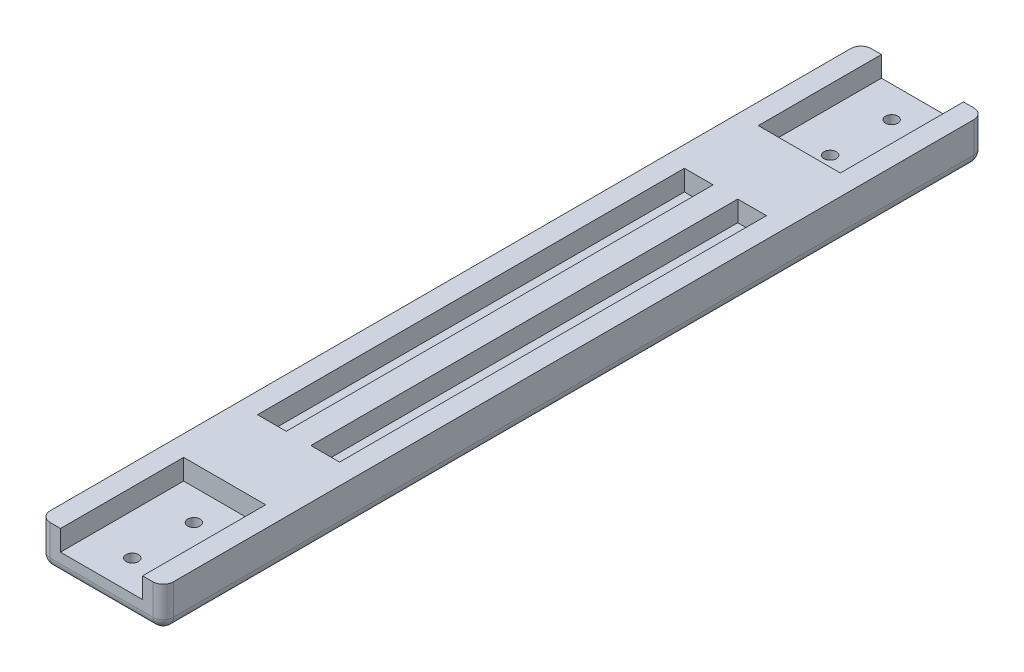
SolidWorks part; units mm, degrees
ref_plane "Front Plane" through (0, 0, 0) normal (0, 0, 1) x (1, 0, 0)
ref_plane "Top Plane" through (0, 0, 0) normal (0, 1, 0) x (1, 0, 0)
ref_plane "Right Plane" through (0, 0, 0) normal (1, 0, 0) x (0, 0, -1)
sketch "Sketch2" plane through (0, 0, 0) normal (0, 1, 0) x (1, 0, 0)
  line L1 (-15, 100) -> (15, 100)
  line L2 (-15, 100) -> (-15, -100)
  line L3 (-15, -100) -> (15, -100)
  line L4 (15, 100) -> (15, -100)
  line L5 (-15, 100) -> (15, -100) construction
  line L6 (-15, -100) -> (15, 100) construction
  point P0 (0, 0)
  dimension "D1" = 30
  dimension "D2" = 200
extrude "Boss-Extrude1" add sketch "Sketch2" along normal blind 10
sketch "Sketch3" plane through (0, 10, 0) normal (0, 1, 0) x (1, 0, 0)
  line L0 (15, 100) -> (-15, 100) construction
  line L1 (-10, 100) -> (10, 100)
  line L2 (-10, 100) -> (-10, 70)
  line L3 (-10, 70) -> (10, 70)
  line L4 (10, 100) -> (10, 70)
  line L5 (-15, 100) -> (-15, -100) construction
  line L6 (-15, -100) -> (15, -100) construction
  line L7 (-10, -100) -> (10, -100)
  line L8 (-10, -100) -> (-10, -70)
  line L9 (-10, -70) -> (10, -70)
  line L10 (10, -100) -> (10, -70)
  line L11 (15, -100) -> (15, 100) construction
  line L12 (3, 52) -> (10, 52)
  line L13 (3, 52) -> (3, -52)
  line L14 (3, -52) -> (10, -52)
  line L15 (10, 52) -> (10, -52)
  line L17 (-10, 52) -> (-3, 52)
  line L18 (-10, 52) -> (-10, -52)
  line L19 (-10, -52) -> (-3, -52)
  line L20 (-3, 52) -> (-3, -52)
  dimension "D1" = 20
  dimension "D2" = 30
  dimension "D3" = 5
  dimension "D4" = 5
  dimension "D5" = 20
  dimension "D6" = 30
  dimension "D7" = 18
  dimension "D8" = 18
  dimension "D9" = 5
  dimension "D10" = 7
  dimension "D11" = 7
  dimension "D12" = 5
  dimension "D13" = 18
  dimension "D14" = 18
extrude "Cut-Extrude1" cut sketch "Sketch3" against normal blind 5
fillet "Fillet1" radius 2.5 4 edges at (-15, 5, 100) (15, 5, 100) (-15, 5, -100) (15, 5, -100)
fillet "Fillet2" radius 2.5 8 edges at (-14.2678, 0, 99.2678) (-15, 0, 0) (-14.2678, 0, -99.2678) (0, 0, -100) (14.2678, 0, -99.2678) (15, 0, 0) (14.2678, 0, 99.2678) (0, 0, 100)
sketch "Sketch4" plane through (0, 10, 0) normal (0, 1, 0) x (1, 0, 0)
  line L0 (-10, 70) -> (10, 70) construction
  line L1 (5, 50) -> (8, 50)
  line L2 (5, 50) -> (5, -50)
  line L3 (5, -50) -> (8, -50)
  line L4 (8, 50) -> (8, -50)
  line L6 (15, -97.5) -> (15, 97.5) construction
  line L8 (-5, -50) -> (-8, -50)
  line L9 (-5, -50) -> (-5, 50)
  line L10 (-5, 50) -> (-8, 50)
  line L11 (-8, -50) -> (-8, 50)
  line L13 (10, 52) -> (3, 52) construction
  line L14 (3, -52) -> (10, -52) construction
  point P16 (-6.5, 50)
  dimension "D1" = 3
  dimension "D2" = 100
  dimension "D3" = 20
  dimension "D4" = 7
  dimension "D5" = 10
  dimension "D6" = 2
  dimension "D7" = 2
extrude "Cut-Extrude2" cut sketch "Sketch4" against normal blind 10
fillet "Fillet3" radius 1.5 8 edges at (5, 2.5, 50) (8, 2.5, 50) (5, 2.5, -50) (8, 2.5, -50) (-5, 2.5, 50) (-8, 2.5, 50) (-8, 2.5, -50) (-5, 2.5, -50)
hole_wizard "Ø3.0mm Dowel Hole1" positions "Sketch7" profile "Sketch6" hole size "Ø3.0" standard "ANSI Metric" end condition through all
sketch "Sketch7" plane through (0, 5, 0) normal (0, 1, 0) x (1, 0, 0)
  line L0 (10, 100) -> (-10, 100) construction
  line L1 (-10, 70) -> (10, 70) construction
  line L2 (10, 70) -> (10, 100) construction
  line L3 (10, 70) -> (10, 100) construction
  line L4 (10, -100) -> (10, -70) construction
  line L5 (10, -100) -> (10, -70) construction
  line L6 (10, -70) -> (-10, -70) construction
  line L7 (-10, -100) -> (10, -100) construction
  point P0 (0, 92.5)
  point P2 (0, 77.5)
  point P4 (0, -77.5)
  point P6 (0, -92.5)
  dimension "D1" = 7.5
  dimension "D2" = 7.5
  dimension "D3" = 10
  dimension "D4" = 10
  dimension "D5" = 10
  dimension "D6" = 10
  dimension "D7" = 7.5
  dimension "D8" = 7.5
sketch "Sketch6" plane through (0, 5, -92.5) normal (1, 0, 0) x (0, 0, 1)
  line L0 (0, 0) -> (0, 5)
  line L1 (0, 5) -> (1.5, 5)
  line L2 (1.5, 5) -> (1.5, 0)
  line L5 (1.5, 0) -> (0, 0)
  line L11 (0, -6.35) -> (0, 107.95) construction
  dimension "Thru Hole Dia." = 3
  dimension "Thru Hole Depth" = 5
